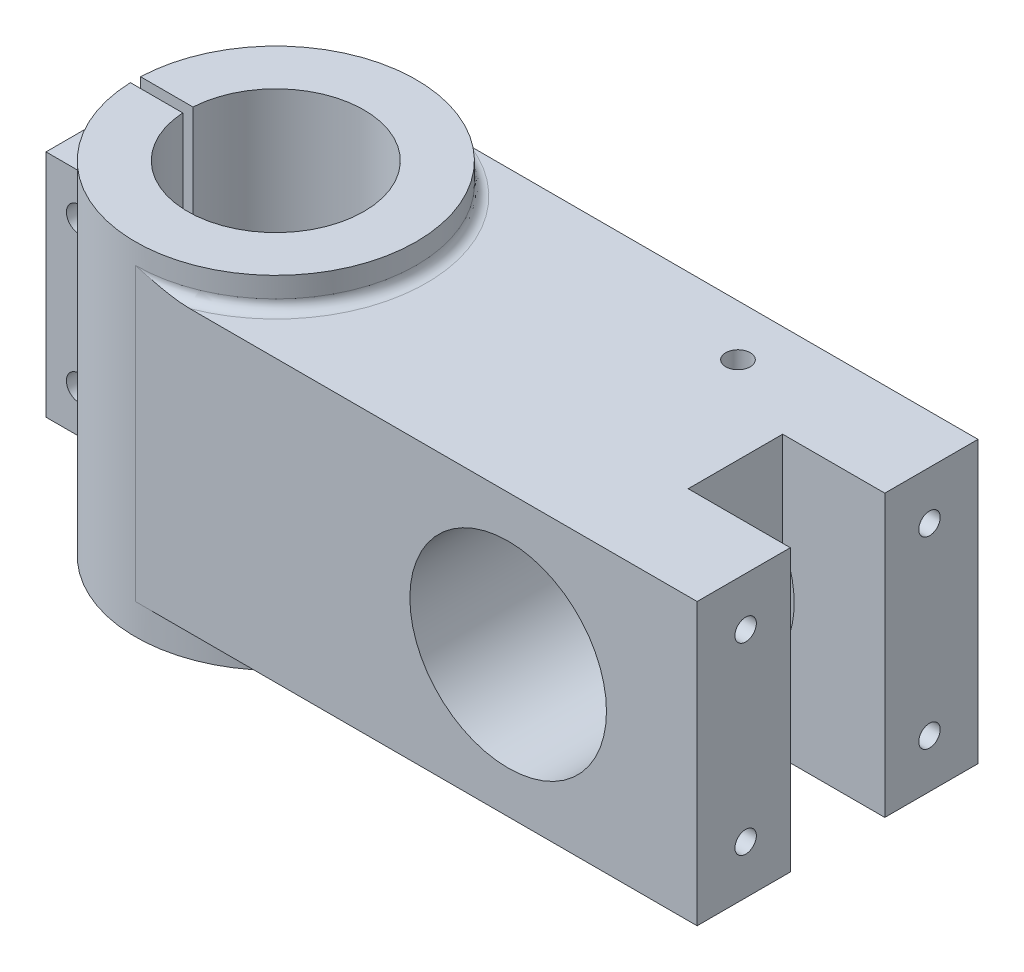
SolidWorks part; units mm, degrees
ref_plane "Front Plane" through (0, 0, 0) normal (0, 0, 1) x (1, 0, 0)
ref_plane "Top Plane" through (0, 0, 0) normal (0, 1, 0) x (1, 0, 0)
ref_plane "Right Plane" through (0, 0, 0) normal (1, 0, 0) x (0, 0, -1)
sketch "Sketch1" plane through (0, 0, 0) normal (0, 1, 0) x (1, 0, 0)
  circle A0 centre (0, 0) radius 27.5
  dimension "D1" = 55
extrude "Boss-Extrude1" add sketch "Sketch1" along normal mid plane 67
sketch "Sketch2" plane through (0, 0, 0) normal (0, 1, 0) x (1, 0, 0)
  line L1 (0, 10) -> (-35, 10)
  line L2 (0, 10) -> (0, -10)
  line L3 (0, -10) -> (-35, -10)
  line L4 (-35, 10) -> (-35, -10)
  point P4 (0, 0)
  dimension "D1" = 35
  dimension "D2" = 20
extrude "Boss-Extrude2" add sketch "Sketch2" along normal mid plane 45
sketch "Sketch3" plane through (0, 0, 0) normal (0, 1, 0) x (1, 0, 0)
  line L1 (0, 27.5) -> (110, 27.5)
  line L2 (0, 27.5) -> (0, -27.5)
  line L3 (0, -27.5) -> (110, -27.5)
  line L4 (110, 27.5) -> (110, -27.5)
  circle A0 centre (0, 0) radius 27.5 construction
  point P4 (46.5891, -13.3808)
  point P5 (0, 0)
  point P8 (0, 0)
  dimension "D1" = 110
extrude "Boss-Extrude3" add sketch "Sketch3" along normal mid plane 55
sketch "Sketch4" plane through (0, 33.5, 0) normal (0, 1, 0) x (1, 0, 0)
  circle A0 centre (0, 0) radius 17.25
  dimension "D1" = 34.5
extrude "Cut-Extrude1" cut sketch "Sketch4" against normal through all
sketch "Sketch5" plane through (0, 0, -27.5) normal (0, 0, -1) x (-1, 0, 0)
  line L0 (-110, 27.5) -> (-110, -27.5) construction
  circle A0 centre (-73, 0) radius 14.5
  point P2 (0, 0)
  dimension "D1" = 29
  dimension "D2" = 37
extrude "Boss-Extrude4" add sketch "Sketch5" along normal blind 12
sketch "Sketch6" plane through (0, 0, -39.5) normal (0, 0, -1) x (-1, 0, 0)
  circle A0 centre (-73, 0) radius 8
  circle A1 centre (-73, 0) radius 14.5 construction
  dimension "D1" = 16
extrude "Cut-Extrude2" cut sketch "Sketch6" against normal through all
sketch "Sketch7" plane through (0, 0, 27.5) normal (0, 0, 1) x (1, 0, 0)
  circle A0 centre (73, 0) radius 19.25
  dimension "D1" = 38.5
extrude "Cut-Extrude3" cut sketch "Sketch7" against normal blind 38.5
sketch "Sketch8" plane through (0, 27.5, 0) normal (0, 1, 0) x (1, 0, 0)
  line L0 (110, -27.5) -> (110, 27.5) construction
  line L1 (110, 9.25) -> (90, 9.25)
  line L2 (110, 9.25) -> (110, -9.25)
  line L3 (110, -9.25) -> (90, -9.25)
  line L4 (90, 9.25) -> (90, -9.25)
  point P6 (90, 0)
  dimension "D1" = 18.5
  dimension "D2" = 20
extrude "Cut-Extrude4" cut sketch "Sketch8" against normal through all
hole_wizard "Tap Drill for M5x0.8 Tap1" positions "Sketch9" profile "Sketch10" hole size "M5x0.8" standard "ANSI Metric"
sketch "Sketch9" plane through (110, 0, 0) normal (1, 0, 0) x (0, 0, -1)
  line L0 (-27.5, 27.5) -> (-9.25, 27.5) construction
  line L1 (-27.5, 27.5) -> (-27.5, -27.5) construction
  point P0 (-18, 18)
  dimension "D1" = 9.5
  dimension "D2" = 9.5
sketch "Sketch10" plane through (110, 18, 18) normal (0, 1, 0) x (0, 0, -1)
  line L0 (0, 0) -> (0, 15.2618)
  line L1 (0, 15.2618) -> (2.1, 14)
  line L2 (2.1, 14) -> (2.1, 0)
  line L5 (2.1, 0) -> (0, 0)
  line L10 (0, 15.2618) -> (-2.1, 14) construction
  line L11 (0, -6.35) -> (0, 107.95) construction
  dimension "Hole Dia." = 4.2
  dimension "Hole Depth" = 14
  dimension "Drill Angle" = 118
pattern_linear "LPattern1" count 2 spacing 36 along (0, 0, -1) count 2 spacing 36 along (0, -1, 0) of "Tap Drill for M5x0.8 Tap1"
hole_wizard "Ø4.8 (4.8) Diameter Hole1" positions "Sketch11" profile "Sketch12" hole size "Ø4.8" standard "ANSI Metric" end condition up to next
sketch "Sketch11" plane through (0, 27.5, 0) normal (0, 1, 0) x (1, 0, 0)
  line L0 (110, 9.25) -> (110, 27.5) construction
  line L1 (110, 27.5) -> (0, 27.5) construction
  point P0 (73, 17.5)
  point P9 (-26.9878, 55.3305)
  dimension "D1" = 37
  dimension "D2" = 10
sketch "Sketch12" plane through (73, 27.5, -17.5) normal (1, 0, 0) x (0, 0, 1)
  line L0 (0, 0) -> (0, 19.5)
  line L1 (0, 19.5) -> (2.4, 19.5)
  line L2 (2.4, 19.5) -> (2.4, 0)
  line L5 (2.4, 0) -> (0, 0)
  line L11 (0, -6.35) -> (0, 107.95) construction
  dimension "Thru Hole Dia." = 4.8
  dimension "Thru Hole Depth" = 19.5
fillet "Fillet1" radius 2 2 edges at (27.5, 27.5, 0) (-27.5, 22.5, 0)
sketch "Sketch13" plane through (0, 0, 0) normal (0, 0, 1) x (1, 0, 0)
  line L1 (0, 42.5) -> (-45, 42.5)
  line L2 (0, 42.5) -> (0, -42.5)
  line L3 (0, -42.5) -> (-45, -42.5)
  line L4 (-45, 42.5) -> (-45, -42.5)
  dimension "D1" = 45
  dimension "D2" = 85
extrude "Cut-Extrude5" cut sketch "Sketch13" against normal mid plane 2
sketch "Sketch14" plane through (0, 0, 10) normal (0, 0, 1) x (1, 0, 0)
  line L0 (0, 0) -> (-28.5, 0) construction
  line L1 (-28.5, 14.3) -> (-28.5, -14.3) construction
  circle A0 centre (-28.5, 14.3) radius 6
  circle A1 centre (-28.5, -14.3) radius 6
  dimension "D3" = 12
  dimension "D1" = 28.6
  dimension "D2" = 28.5
extrude "Cut-Extrude6" cut sketch "Sketch14" along normal up to next
hole_wizard "M6x1.0 Tapped Hole1" positions "Sketch15" profile "Sketch16" tap size "M6x1.0" standard "ANSI Metric" end condition through all
sketch "Sketch15" plane through (0, 0, 10) normal (0, 0, 1) x (1, 0, 0)
  line L0 (-28.5, 14.3) -> (-28.5, -14.3) construction
  line L2 (0, 0) -> (-28.5, 0) construction
  point P0 (-28.5, 14.3)
  point P2 (-28.5, -14.3)
  dimension "D1" = 28.5
  dimension "D2" = 28.6
sketch "Sketch16" plane through (-28.5, 14.3, 10) normal (1, 0, 0) x (0, -1, 0)
  line L0 (0, 0) -> (0, 49.5)
  line L1 (0, 49.5) -> (2.5, 49.5)
  line L2 (2.5, 49.5) -> (2.5, 0)
  line L5 (2.5, 0) -> (0, 0)
  line L11 (0, -6.35) -> (0, 107.95) construction
  dimension "Thru Tap Drill Dia." = 5
  dimension "Thru Tap Drill Depth" = 49.5
cosmetic thread "Hole Thread1" parameters "D2"=6
cosmetic thread "Hole Thread2" parameters "D2"=6
